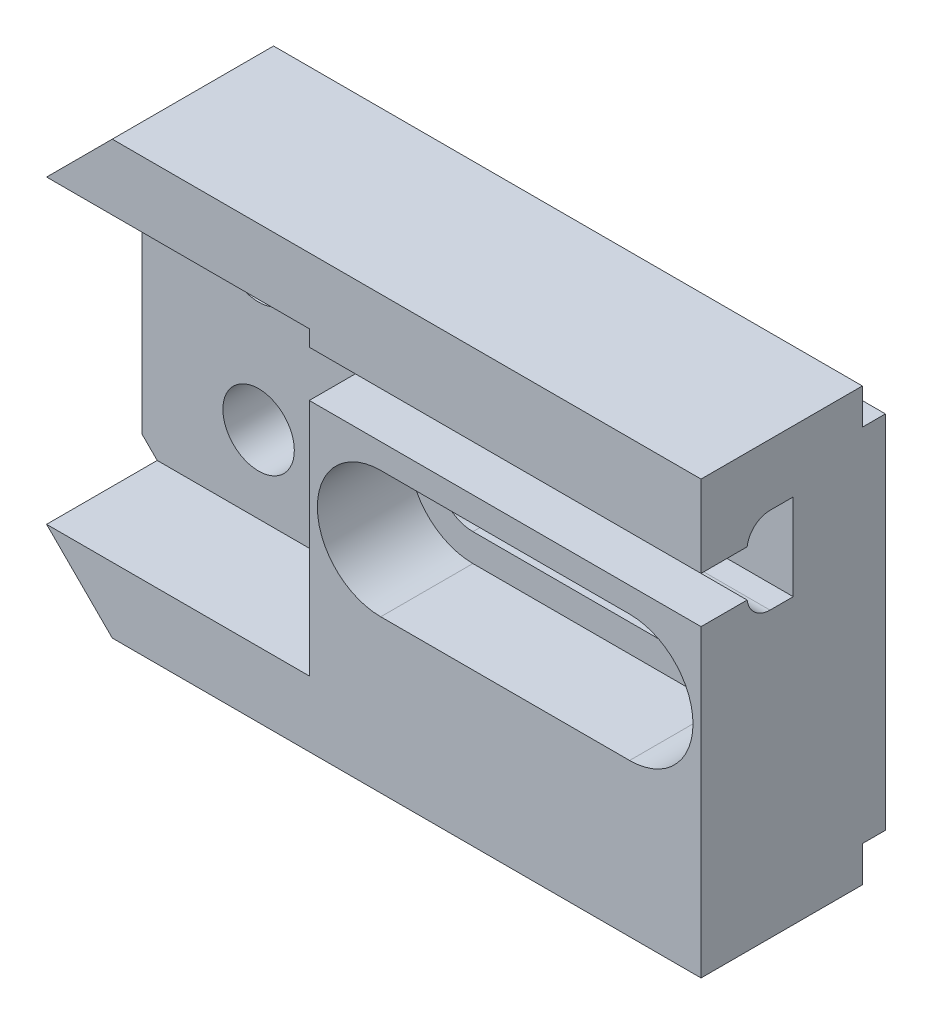
SolidWorks part; units mm, degrees
ref_plane "Front Plane" through (0, 0, 0) normal (0, 0, 1) x (1, 0, 0)
ref_plane "Top Plane" through (0, 0, 0) normal (0, 1, 0) x (1, 0, 0)
ref_plane "Right Plane" through (0, 0, 0) normal (1, 0, 0) x (0, 0, -1)
sketch "ProfileSketch3" plane through (0, 0, 0) normal (0, 0, 1) x (1, 0, 0)
  line L0 (0, 18.75) -> (29.05, 18.75)
  line L1 (0, 0) -> (29.05, 0)
  line L2 (0, 0) -> (0, 18.75)
  line L4 (29.05, 0) -> (29.05, 18.75)
  line L12 (15.15, 9.375) -> (25.95, 9.375) construction
  line L13 (15.15, 10.925) -> (25.95, 10.925)
  line L14 (15.15, 7.825) -> (25.95, 7.825)
  arc A6 (15.15, 10.925) -> (15.15, 7.825) centre (15.15, 9.375) ccw
  arc A7 (25.95, 7.825) -> (25.95, 10.925) centre (25.95, 9.375) ccw
  point P12 (20.55, 9.375)
  dimension "D2" = 3.1
  dimension "D6" = 29.05
  dimension "D1" = 18.75
  dimension "D5" = 9.375
  dimension "D7" = 15.15
  dimension "D3" = 3.1
extrude "ProfileBoss-Extrude1" add sketch "ProfileSketch3" along normal blind 8
sketch "MicroSwitchCutSketch4" plane through (0, 0, 8) normal (0, 0, 1) x (1, 0, 0)
  line L0 (29.05, 18.75) -> (0, 18.75) construction
  line L1 (0, 15.9) -> (12.05, 15.9)
  line L2 (0, 15.9) -> (0, 2.85)
  line L3 (0, 2.85) -> (12.05, 2.85)
  line L4 (12.05, 15.9) -> (12.05, 2.85)
  dimension "D1" = 12.05
  dimension "D2" = 13.05
  dimension "D3" = 2.85
extrude "MicroSwitchCut-Extrude1" cut sketch "MicroSwitchCutSketch4" against normal blind 4.8
sketch "Sketch5" plane through (0, 0, 3.2) normal (0, 0, 1) x (1, 0, 0)
  line L0 (0, 2.85) -> (12.05, 2.85) construction
  line L2 (12.05, 2.85) -> (12.05, 15.9) construction
  line L4 (12.05, 15.9) -> (0, 15.9) construction
  circle A0 centre (5.05, 12.55) radius 1.55
  circle A1 centre (5.05, 6.2) radius 1.55
  point P10 (11.05, 8.8)
  point P11 (0, 8.8)
  point P12 (15, 21.85)
  point P13 (11.05, 21.85)
  point P14 (15, 0)
  point P15 (15, 21.85)
  point P16 (0, 0)
  point P17 (15, 0)
  point P18 (0, 8.8)
  point P19 (0, 0)
  point P20 (-1, 8.8)
  point P21 (0, 8.8)
  point P22 (-1, 21.85)
  point P23 (-1, 8.8)
  point P24 (15, 21.85)
  point P25 (-1, 21.85)
  point P26 (15, 0)
  point P27 (15, 21.85)
  point P28 (0, 0)
  point P29 (15, 0)
  point P30 (0, 8.8)
  point P31 (0, 0)
  point P32 (11.05, 21.85)
  point P33 (-1, 21.85)
  point P34 (11.05, 8.8)
  point P35 (11.05, 21.85)
  point P36 (-1, 8.8)
  point P37 (0, 8.8)
  point P38 (0, 8.8)
  point P39 (11.05, 8.8)
  point P40 (-1, 21.85)
  point P41 (-1, 8.8)
  point P42 (11.05, 8.8)
  point P43 (11.05, 21.85)
  point P44 (0, 0)
  point P45 (15, 0)
  point P46 (0, 0)
  point P47 (0, 8.8)
  point P48 (-1, 21.85)
  point P49 (15, 21.85)
  point P50 (15, 0)
  point P51 (15, 21.85)
  point P52 (-1, 21.85)
  point P53 (-1, 8.8)
  point P54 (-1, 8.8)
  point P55 (0, 8.8)
  point P56 (-1, 21.85)
  point P57 (-1, 8.8)
  point P58 (-1, 21.85)
  point P59 (11.05, 21.85)
  point P60 (-1, 21.85)
  point P61 (-1, 8.8)
  point P62 (-1, 8.8)
  point P63 (11.05, 8.8)
  point P64 (11.05, 21.85)
  point P65 (11.05, 8.8)
  point P66 (2.75, 0)
  point P67 (-2.75, 0)
  point P68 (0, -2.75)
  point P69 (0, 2.75)
  dimension "D4" = 3.1
  dimension "D3" = 7
  dimension "D2" = 3.35
  dimension "D1" = 3.35
extrude "MicroSwitchMountingHolesCut-Extrude2" cut sketch "Sketch5" against normal blind 3.1
sketch "SmallChannelCableSketch6" plane through (0, 0, 8) normal (0, 0, 1) x (1, 0, 0)
  line L0 (12.05, 2.85) -> (12.05, 15.9) construction
  line L1 (12.05, 15.2046) -> (29.05, 15.2046)
  line L2 (12.05, 15.2046) -> (12.05, 13.2046)
  line L3 (12.05, 13.2046) -> (29.05, 13.2046)
  line L4 (29.05, 15.2046) -> (29.05, 13.2046)
  line L5 (29.05, 0) -> (29.05, 18.75) construction
  point P10 (1, 21.85)
  point P11 (1, 13.05)
  point P12 (16, 21.85)
  point P13 (1, 21.85)
  point P14 (16, 0)
  point P15 (16, 21.85)
  point P16 (12.05, 0)
  point P17 (16, 0)
  point P18 (1, 13.05)
  point P19 (0, 13.05)
  point P20 (1, 21.85)
  point P21 (1, 13.05)
  point P22 (16, 21.85)
  point P23 (1, 21.85)
  point P24 (16, 0)
  point P25 (16, 21.85)
  point P26 (0, 0)
  point P27 (16, 0)
  point P28 (0, 13.05)
  point P29 (0, 0)
  point P30 (12.05, 13.05)
  point P31 (1, 13.05)
  point P32 (1, 13.05)
  point P33 (0, 13.05)
  point P34 (12.05, 0)
  point P35 (12.05, 13.05)
  point P36 (0, 0)
  point P37 (12.05, 0)
  point P38 (0, 13.05)
  point P39 (0, 0)
  point P40 (12.05, 13.05)
  point P41 (1, 13.05)
  point P42 (12.05, 0)
  point P43 (12.05, 13.05)
  point P44 (5.05, 9.7)
  point P45 (6.5323, 10.1532)
  point P46 (5.05, 3.35)
  point P47 (6.5323, 3.8032)
  point P48 (5.05, 9.7)
  point P49 (6.5323, 10.1532)
  point P50 (5.05, 3.35)
  point P51 (6.5323, 3.8032)
  point P52 (0, 0)
  point P53 (16, 0)
  point P54 (0, 0)
  point P55 (0, 13.05)
  point P56 (1, 21.85)
  point P57 (16, 21.85)
  point P58 (16, 0)
  point P59 (16, 21.85)
  point P60 (1, 21.85)
  point P61 (1, 13.05)
  point P62 (1, 13.05)
  point P63 (0, 13.05)
extrude "SmallChannelCableCut-Extrude3" cut sketch "SmallChannelCableSketch6" against normal blind 2
sketch "LargeChannelCableSketch7" plane through (0, 0, 6) normal (0, 0, 1) x (1, 0, 0)
  line L0 (12.05, 15.2046) -> (12.05, 15.9) construction
  line L1 (12.05, 16.0796) -> (29.05, 16.0796)
  line L2 (12.05, 16.0796) -> (12.05, 12.3296)
  line L3 (12.05, 12.3296) -> (29.05, 12.3296)
  line L4 (29.05, 16.0796) -> (29.05, 12.3296)
  line L5 (29.05, 0) -> (29.05, 13.2046) construction
  line L6 (29.05, 15.2046) -> (12.05, 15.2046) construction
  dimension "D1" = 0.875
  dimension "D2" = 3.75
extrude "LargeChannelCableCut-Extrude4" cut sketch "LargeChannelCableSketch7" against normal blind 2
chamfer "Chamfer2" distance 3.5 angle 45 2 edges at (0, 18.75, 4) (0, 0, 4)
fillet "Fillet3" radius 1 2 edges at (20.55, 16.0796, 6) (20.55, 12.3296, 6)
chamfer "Chamfer1" distance 1 angle 45 1 edges at (12.05, 14.1148, 4)
sketch "Sketch6" plane through (0, 0, 8) normal (0, 0, 1) x (1, 0, 0)
  line L3 (15.15, 9.375) -> (25.95, 9.375) construction
  line L4 (15.15, 12.125) -> (25.95, 12.125)
  line L5 (15.15, 6.625) -> (25.95, 6.625)
  arc A2 (15.15, 12.125) -> (15.15, 6.625) centre (15.15, 9.375) ccw
  arc A3 (25.95, 6.625) -> (25.95, 12.125) centre (25.95, 9.375) ccw
  point P9 (20.55, 9.375)
extrude "MountSLotBoreCut-Extrude1" cut sketch "Sketch6" against normal blind 4
sketch "Sketch8" plane through (0, 0, 0) normal (0, 0, -1) x (-1, 0, 0)
  line L0 (-29.05, 18.75) -> (-3.5, 18.75)
  line L1 (-3.5, 18.75) -> (-1.95, 17.2)
  line L2 (0, 15.25) -> (-3.5, 18.75) construction
  line L3 (-1.95, 17.2) -> (-29.05, 17.2)
  line L4 (-29.05, 0) -> (-29.05, 18.75) construction
  line L5 (-29.05, 17.2) -> (-29.05, 18.75)
  line L6 (-29.05, 0) -> (-3.5, 0)
  line L7 (-3.5, 0) -> (-1.95, 1.55)
  line L8 (-3.5, 0) -> (0, 3.5) construction
  line L9 (-1.95, 1.55) -> (-29.05, 1.55)
  line L10 (-29.05, 1.55) -> (-29.05, 0)
  dimension "D1" = 1.55
  dimension "D2" = 15.65
extrude "SlidingMountCut-Extrude1" cut sketch "Sketch8" against normal blind 1
equation "\"SK8RodShaftSupportHeight\"= 42mm"
equation "\"SK8RodShaftSupportLength\"= 15mm"
equation "\"SK8MountHoleDiameter\"= 5mm"
equation "\"SK8RiserWidth\"= 6.75mm'Measured to meet Nema17 Mount Hole Center axis"
equation "\"SK8MountHoleFromSide\"= \"SK8RodShaftSupportLength\" / 2"
equation "\"SK8MountHoleFromEitherEnd\"= 5.5mm"
equation "\"MicroSwitchCutOutLength\"= 13.05mm"
equation "\"MicroSwitchHeight\"= 6.55mm"
equation "\"MicroSwitchMountingHoleOffsetFromSide\"= 3.35mm"
equation "\"MicroSwitchTerminalHeight\"= 3.5mm"
equation "\"MicroSwitchExtraMountingHeight\"= 2mm"
equation "\"MicroSwitchDepth\"= 2.8mm"
equation "\"MicroSwitchMountingHoleOffsetFromBottom\"= 7mm"
equation "\"M2HeatInsertHoleDiameter\"= 3mm + .1mm'Add .1mm for printing"
equation "\"M2HeatInsertHoleDepth\"= 3.1mm'Spec"
equation "\"D1@ProfileBoss-Extrude1\" = \"SK8RiserWidth\""
equation "\"D1@MicroSwitchCutSketch4\"=\"MicroSwitchCutOutHeight\""
equation "\"D2@MicroSwitchCutSketch4\" = \"MicroSwitchCutOutLength\""
equation "\"D1@MicroSwitchCut-Extrude1\"=\"MicroSwitchDepth\" + 2mm"
equation "\"D3@Sketch5\"=\"MicroSwitchMountingHoleOffsetFromBottom\""
equation "\"D4@Sketch5\"=\"M2HeatInsertHoleDiameter\""
equation "\"D1@MicroSwitchMountingHolesCut-Extrude2\" = \"M2HeatInsertHoleDepth\""
equation "\"MicroSwitchCutOutHeight\"= \"MicroSwitchExtraMountingHeight\" + \"MicroSwitchTerminalHeight\" + \"MicroSwitchHeight\""
equation "\"EndStopCableWidth\"= 3.75mm"
equation "\"D1@SmallChannelCableSketch6\" = \"EndStopCableDepth\""
equation "\"EndStopCableDepth\"= 2mm"
equation "\"D1@SmallChannelCableCut-Extrude3\"=\"EndStopCableDepth\""
equation "\"D1@LargeChannelCableSketch7\" =  ( \"EndStopCableWidth\" - \"EndStopCableDepth\" )  / 2"
equation "\"D2@LargeChannelCableSketch7\" = \"EndStopCableWidth\""
equation "\"D1@LargeChannelCableCut-Extrude4\" = \"EndStopCableDepth\""
equation "\"D6@ProfileSketch3\"= \"YAxisEndStopMicroSwitchHolderWidth\""
equation "\"D2@Sketch5\"=\"MicroSwitchMountingHoleOffsetFromSide\""
equation "\"D1@ProfileSketch3\"=\"YAxisEndStopMicroSwitchHolderHeight\""
equation "\"Nema17StepperMountSlotDistance\"=31"
equation "\"YAxisEndStopMicroSwitchHolderHeight\"= 18.75'Same as XAxisMircoSwitchHolder"
equation "\"M3ScrewDiameter\"= 3mm + .1mm'Add .1mm for printing"
equation "\"D3@MicroSwitchCutSketch4\"=(\"YAxisEndStopMicroSwitchHolderHeight\"-\"MicroSwitchCutOutLength\")/2"
equation "\"D5@ProfileSketch3\"=\"YAxisEndStopMicroSwitchHolderHeight\"/2"
equation "\"D7@ProfileSketch3\"=\"MicroSwitchCutOutHeight\" + \"M3ScrewDiameter\""
equation "\"YAxisEndStopHolderDistanceBetweenMountingScrews\"= 10mm"
equation "\"D1@Sketch5\"=\"MicroSwitchMountingHoleOffsetFromSide\""
equation "\"YAxisEndStopMicroSwitchHolderThickness\"= 8mm"
equation "\"YAxisEndStopMicroSwitchHolderWidth\"= 29.05mm'Same as XAxisMicroSwitchHolder"
equation "\"D2@ProfileSketch3\"=\"M2HeatInsertHoleDiameter\""
equation "\"D3@ProfileSketch3\"=\"M3ScrewDiameter\""
equation "\"EndStopSlidingMountWallWidth\" = 1.5mm"
equation "\"D1@Sketch8\"=\"EndStopSlidingMountWallWidth\" + \"EndStopSlidingMountWallPrintOffset\""
equation "\"EndStopSlidingMountWallPrintOffset\"= .05mm"
equation "\"EndStopSlidingMountWallDepth\"= 1mm"
equation "\"D1@SlidingMountCut-Extrude1\"=\"EndStopSlidingMountWallDepth\""
